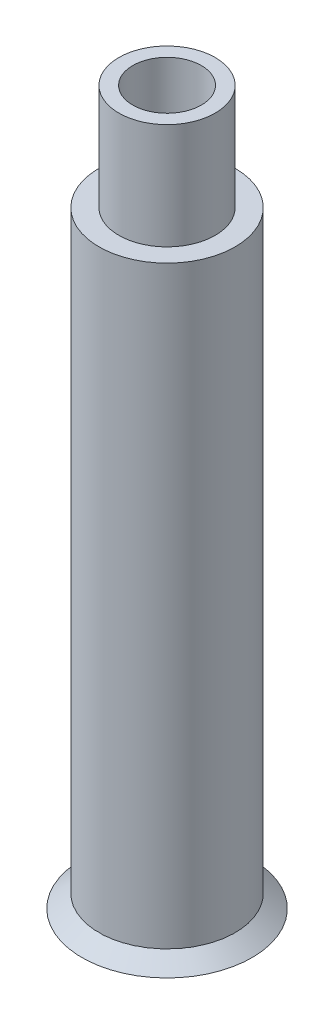
SolidWorks part; units mm, degrees
ref_plane "Front Plane" through (0, 0, 0) normal (0, 0, 1) x (1, 0, 0)
ref_plane "Top Plane" through (0, 0, 0) normal (0, 1, 0) x (1, 0, 0)
ref_plane "Right Plane" through (0, 0, 0) normal (1, 0, 0) x (0, 0, -1)
sketch "Sketch1" plane through (0, 0, 0) normal (0, 1, 0) x (1, 0, 0)
  circle A0 centre (0, 0) radius 6.35
  dimension "D1" = 12.7
extrude "Boss-Extrude1" add sketch "Sketch1" along normal blind 56.642
sketch "Sketch2" plane through (0, 0, 0) normal (1, 0, 0) x (0, 0, -1)
  line L0 (-3.2004, 2.2749) -> (-4.1735, 2.2749)
  line L1 (-4.1735, 2.2749) -> (-7.8359, 0)
  line L3 (-4.4958, 2.665) -> (-7.9375, 0)
  line L4 (-7.9375, 0) -> (-7.8359, 0)
  line L5 (-4.5223, 2.665) -> (-3.2004, 2.665)
  line L7 (-4.4958, 2.665) -> (-4.4958, 66.5239)
  line L8 (-4.4958, 66.5239) -> (-3.2004, 66.5239)
  line L9 (-3.2004, 66.5239) -> (-3.2004, 2.665)
  line L11 (-6.35, 0) -> (6.35, 0) construction
  line L13 (-3.2004, 2.2749) -> (-3.2004, 2.665)
  line L14 (0, 0) -> (0, 4.302)
  dimension "D1" = 4.4958
  dimension "D2" = 3.2004
  dimension "D3" = 0.1016
  dimension "D4" = 7.9375
  dimension "D5" = 63.8589
revolve "Revolve1" add sketch "Sketch2" angle 360 about L14 region at (0, 1.8068, 5.1425) region at (0, 34.5945, 3.8481)
sketch "Sketch4" plane through (0, 66.5239, 0) normal (0, 1, 0) x (1, 0, 0)
  circle A0 centre (0, 0) radius 3.2004
  dimension "D1" = 6.4008
